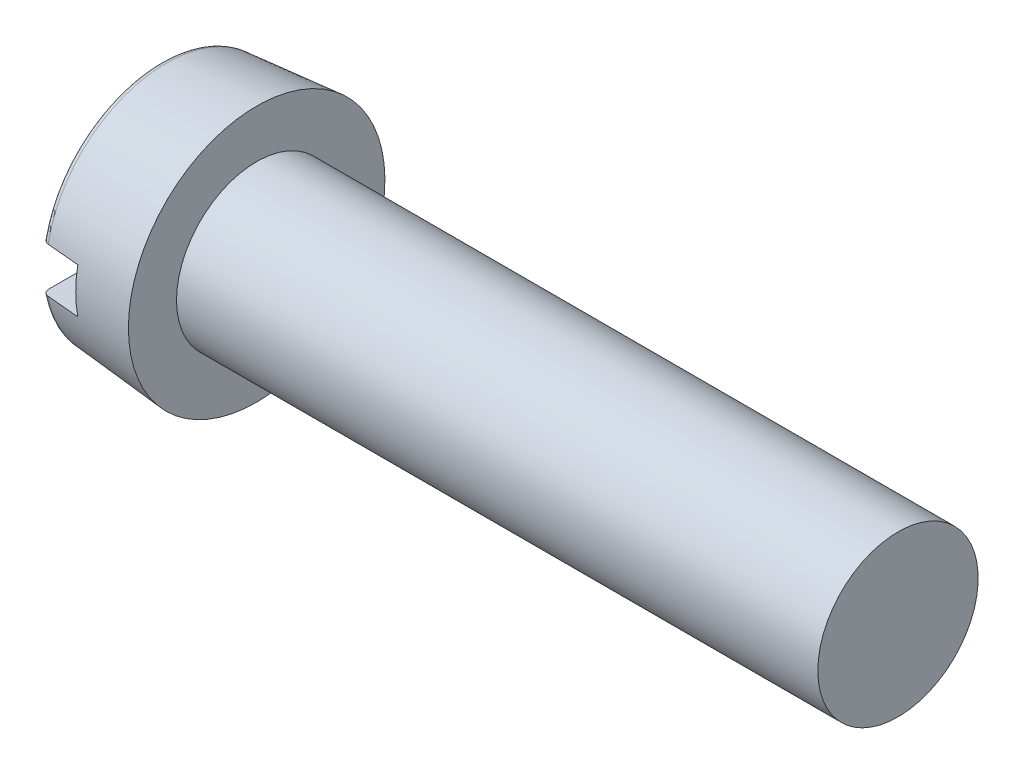
SolidWorks part; units mm, degrees
ref_plane "Front Plane" through (0, 0, 0) normal (0, 0, 1) x (1, 0, 0)
ref_plane "Top Plane" through (0, 0, 0) normal (0, 1, 0) x (1, 0, 0)
ref_plane "Right Plane" through (0, 0, 0) normal (1, 0, 0) x (0, 0, -1)
sketch "BodySke" plane through (0, 0, 0) normal (0, 0, 1) x (1, 0, 0)
  line L0 (0, 0) -> (111.3824, 0) construction
  line L1 (0, 0) -> (0, 7.4751)
  line L2 (0, 7.4751) -> (6, 8)
  line L3 (6, 8) -> (6, 5)
  line L4 (6, 5) -> (46, 5)
  line L5 (46, 5) -> (46, 0)
  line L6 (7.5, 8.824) -> (7.5, -5.8939) construction
  line L7 (0, 0) -> (46, 0)
  line L8 (9, 8.824) -> (9, -4.958) construction
  point P10 (46, 4.172)
  dimension "Thread_minor" = 8.344
  dimension "Advance" = 1.5
revolve "BaseBody" add sketch "BodySke" angle 360 about L0
cosmetic thread "ThreadCosmetic" [suppressed] parameters "Thread_minor"=8.344
fillet "Fillet1" radius 0.4 1 edges at (0, 0, 7.4751)
sketch "SlotSke" plane through (0, 0, 0) normal (-1, 0, 0) x (0, 0, 1)
  line L1 (-8, 1.405) -> (8, 1.405)
  line L2 (-8, 1.405) -> (-8, -1.405)
  line L3 (-8, -1.405) -> (8, -1.405)
  line L4 (8, 1.405) -> (8, -1.405)
  dimension "D1" = 16
  dimension "D2" = 8
  dimension "D3" = 1.405
extrude "Slot" cut sketch "SlotSke" against normal blind 2.4
sketch "ThdSchSke" plane through (0, 0, 0) normal (0, 0, 1) x (1, 0, 0)
  line L0 (0, 0) -> (55.1256, 0) construction
  line L1 (0, 0) -> (111.3824, 0) construction
  line L2 (45.522, 5) -> (45.522, 5.9561)
  line L3 (45.522, 5.9561) -> (46.478, 5.9561)
  line L4 (46.478, 5.9561) -> (46.478, 5)
  line L5 (46.478, 5) -> (46, 4.172)
  line L6 (46, 4.172) -> (45.522, 5)
  line L7 (6, 5) -> (46, 5) construction
  line L13 (46, 5) -> (46, 0) construction
revolve "ThreadSchematic" [suppressed] cut sketch "ThdSchSke" angle 360 about L0
pattern_linear "ThdSchPat" [suppressed] count 25 along (-1, 0, 0) of bodies 103
equation "\"Thread_minor@ThreadCosmetic\" = \"Thread_minor@BodySke\""
equation "\"D1@SlotSke\" = \"Head_dia@BodySke\""
equation "\"D2@SlotSke\" = \"D1@SlotSke\" / 2"
equation "\"D3@SlotSke\" = \"Slot_width@SlotSke\" / 2"
equation "\"Advance@ThdSchPat\" = \"Advance@BodySke\""
equation "\"D1@ThdSchPat\" =  int(  ( \"Length@BodySke\" - \"Thread_runout@BodySke\" )  / \"Advance@ThdSchPat\" )  + 1"
